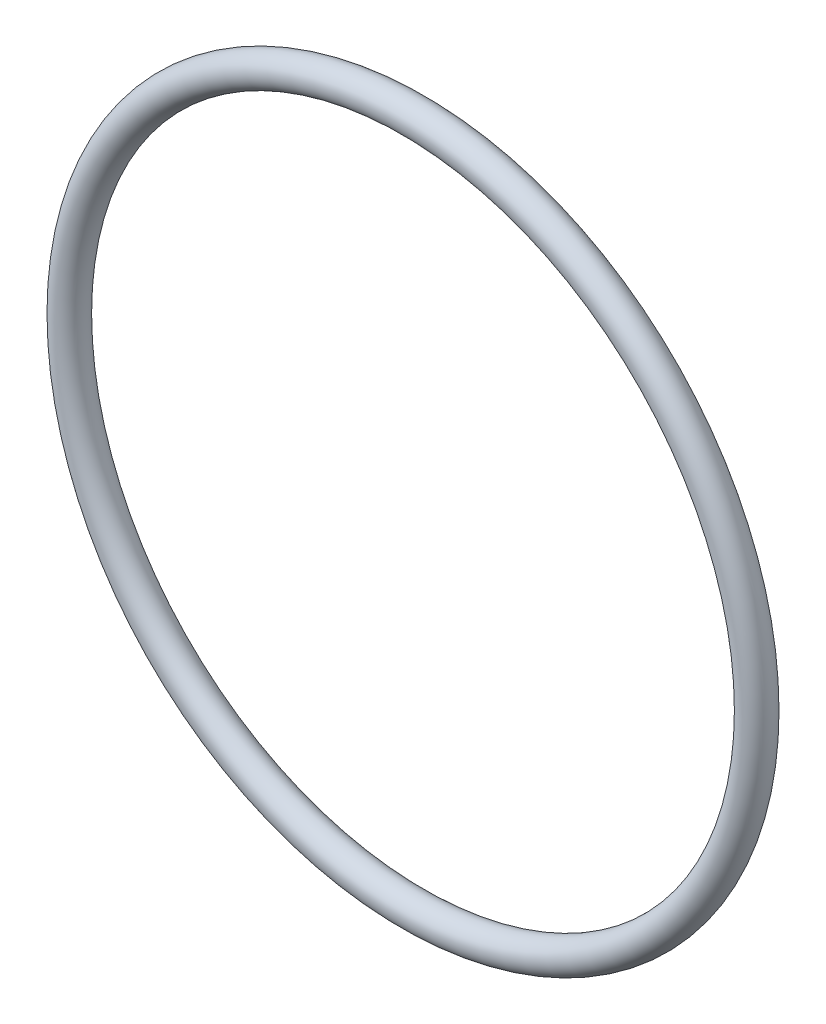
SolidWorks part; units mm, degrees
ref_plane "Front" through (0, 0, 0) normal (0, 0, 1) x (1, 0, 0)
ref_plane "Top" through (0, 0, 0) normal (0, 1, 0) x (1, 0, 0)
ref_plane "Right" through (0, 0, 0) normal (1, 0, 0) x (0, 0, -1)
sketch "Sketch1" plane through (0, 0, 0) normal (0, 0, 1) x (1, 0, 0)
  circle A0 centre (0, 0) radius 32.2
  dimension "d1" = 64.4
sketch "Sketch2" plane through (0, 0, 0) normal (0, 1, 0) x (1, 0, 0)
  circle A0 centre (-33.75, 0) radius 1.55
  point P2 (-32.2, 0)
  dimension "d2" = 3.1
sweep "Sweep1" add profiles "Sketch2" path "Sketch1"
ref_axis "Axis1" through (0, 0, -4.8575) along (0, 0, 1)
